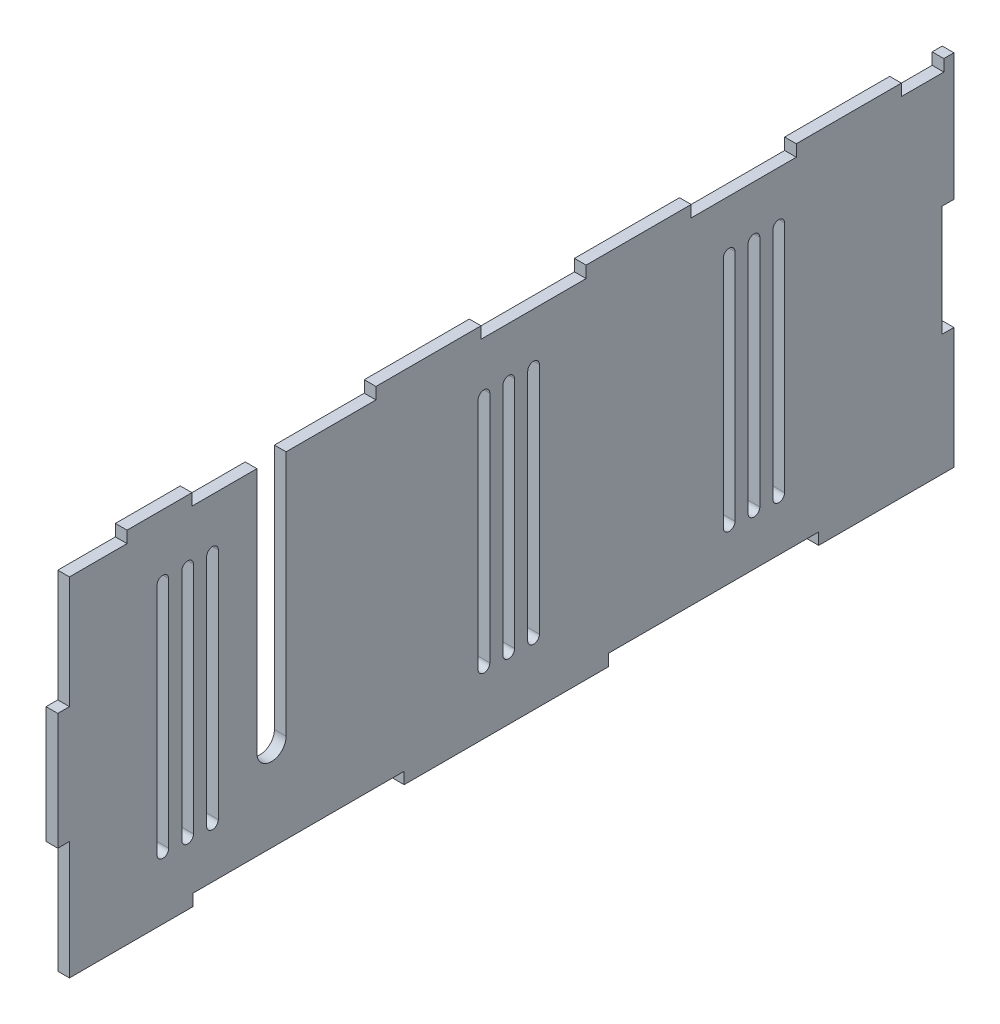
SolidWorks part; units mm, degrees
ref_plane "Front Plane" through (0, 0, 0) normal (0, 0, 1) x (1, 0, 0)
ref_plane "Top Plane" through (0, 0, 0) normal (0, 1, 0) x (1, 0, 0)
ref_plane "Right Plane" through (0, 0, 0) normal (1, 0, 0) x (0, 0, -1)
sketch "Sketch1" plane through (0, 0, 0) normal (1, 0, 0) x (0, 0, -1)
  line L1 (0, 0) -> (307, 0)
  line L2 (0, 0) -> (0, 115)
  line L3 (0, 115) -> (307, 115)
  line L4 (307, 0) -> (307, 115)
  dimension "D1" = 307
  dimension "D2" = 115
extrude "Boss-Extrude1" add sketch "Sketch1" along normal blind 4
sketch "Sketch2" plane through (0, 0, 0) normal (-1, 0, 0) x (0, 0, 1)
  line L0 (-73.2167, 30.5919) -> (-73.2167, 113) construction
  line L1 (-78.2167, 30.5919) -> (-78.2167, 118.2888)
  line L2 (-68.2167, 30.5919) -> (-68.2167, 118.2888)
  line L3 (-139, 113) -> (-121, 113) construction
  line L4 (-78.2167, 118.2888) -> (-68.2167, 118.2888)
  arc A0 (-78.2167, 30.5919) -> (-68.2167, 30.5919) centre (-73.2167, 30.5919) ccw
  point P2 (-73.2167, 71.796)
  point P7 (-73.2167, 113)
  dimension "D1" = 10
extrude "Cut-Extrude1" cut sketch "Sketch2" against normal blind 4
sketch "Sketch3" plane through (0, 0, 0) normal (-1, 0, 0) x (0, 0, 1)
  line L0 (0, 36.5) -> (0, -4)
  line L1 (0, 115) -> (-4, 115)
  line L2 (0, 115) -> (0, 76.5)
  line L3 (0, 76.5) -> (-4, 76.5)
  line L4 (-4, 115) -> (-4, 76.5)
  line L9 (0, 36.5) -> (-4, 36.5)
  line L10 (-4, 36.5) -> (-4, -4)
  line L11 (0, 115) -> (0, 0) construction
  line L12 (-68.2167, 115) -> (0, 115) construction
  line L13 (0, -4) -> (-4, -4)
  dimension "D1" = 4
  dimension "D2" = 38.5
  dimension "D3" = 40
extrude "Cut-Extrude2" cut sketch "Sketch3" against normal blind 4
sketch "Sketch4" plane through (0, 0, 0) normal (-1, 0, 0) x (0, 0, 1)
  line L1 (-307, 0) -> (-260.6667, 0)
  line L2 (-307, 0) -> (-307, -4)
  line L3 (-307, -4) -> (-260.6667, -4)
  line L4 (-260.6667, 0) -> (-260.6667, -4)
  line L11 (-4, 0) -> (-46.33, 0)
  line L12 (-4, 0) -> (-4, -4)
  line L13 (-4, -4) -> (-46.33, -4)
  line L14 (-46.33, 0) -> (-46.33, -4)
  dimension "D1" = 46.3333
  dimension "D2" = 4
  dimension "D3" = 42.33
  dimension "D4" = 4
extrude "Boss-Extrude3" add sketch "Sketch4" against normal blind 4 contours L2 L1 L4 L3 | L12 L11 L14 L13
sketch "Sketch5" plane through (0, 0, 0) normal (-1, 0, 0) x (0, 0, 1)
  line L0 (-307, 115) -> (-78.2167, 115) construction
  line L1 (-289, 115) -> (-253, 115)
  line L2 (-289, 115) -> (-289, 119)
  line L3 (-289, 119) -> (-253, 119)
  line L4 (-253, 115) -> (-253, 119)
  line L5 (-307, -4) -> (-307, 115) construction
  dimension "D1" = 4
  dimension "D2" = 36
  dimension "D3" = 18
extrude "Boss-Extrude4" add sketch "Sketch5" against normal blind 4
sketch "Sketch7" plane through (0, 0, 0) normal (-1, 0, 0) x (0, 0, 1)
  line L0 (-68.2167, 115) -> (-4, 115) construction
  line L1 (-45.9767, 115) -> (-23.7367, 115)
  line L2 (-45.9767, 115) -> (-45.9767, 119)
  line L3 (-45.9767, 119) -> (-23.7367, 119)
  line L4 (-23.7367, 115) -> (-23.7367, 119)
  line L5 (-68.2167, 30.5919) -> (-68.2167, 115) construction
  dimension "D1" = 22.24
  dimension "D2" = 22.24
  dimension "D3" = 4
extrude "Boss-Extrude6" add sketch "Sketch7" against normal blind 4
sketch "Sketch8" plane through (0, 0, 0) normal (-1, 0, 0) x (0, 0, 1)
  line L0 (-307, -4) -> (-307, 115) construction
  line L1 (-307, 75.5) -> (-303, 75.5)
  line L2 (-307, 75.5) -> (-307, 37.5)
  line L3 (-307, 37.5) -> (-303, 37.5)
  line L4 (-303, 75.5) -> (-303, 37.5)
  line L5 (-307, 115) -> (-289, 115) construction
  dimension "D1" = 38
  dimension "D2" = 39.5
extrude "Cut-Extrude3" cut sketch "Sketch8" against normal blind 4
pattern_linear "LPattern1" count 3 spacing 72 along (0, 0, 1) of "Boss-Extrude4"
sketch "Sketch9" plane through (0, 0, 0) normal (-1, 0, 0) x (0, 0, 1)
  line L0 (-46.33, 0) -> (-260.6667, 0) construction
  line L1 (-188.6667, 0) -> (-118.6667, 0)
  line L2 (-188.6667, 0) -> (-188.6667, -4)
  line L3 (-188.6667, -4) -> (-118.6667, -4)
  line L4 (-118.6667, 0) -> (-118.6667, -4)
  line L5 (-260.6667, 0) -> (-260.6667, -4) construction
  point P6 (-153.6667, 0)
  dimension "D1" = 70
  dimension "D2" = 107
  dimension "D3" = 4
extrude "Boss-Extrude7" add sketch "Sketch9" against normal blind 4
sketch "Sketch10" plane through (0, 0, 0) normal (-1, 0, 0) x (0, 0, 1)
  line L0 (-247, 97.5) -> (-247, 17.5) construction
  line L1 (-245, 97.5) -> (-245, 17.5)
  line L2 (-249, 97.5) -> (-249, 17.5)
  line L3 (-307, 75.5) -> (-307, 115) construction
  line L4 (-307, -4) -> (-260.6667, -4) construction
  line L6 (-240.5, 97.5) -> (-240.5, 17.5)
  line L7 (-236.5, 97.5) -> (-236.5, 17.5)
  line L8 (-238.5, 97.5) -> (-238.5, 17.5) construction
  line L9 (-232, 97.5) -> (-232, 17.5)
  line L10 (-228, 97.5) -> (-228, 17.5)
  line L11 (-230, 97.5) -> (-230, 17.5) construction
  arc A0 (-245, 97.5) -> (-249, 97.5) centre (-247, 97.5) ccw
  arc A1 (-249, 17.5) -> (-245, 17.5) centre (-247, 17.5) ccw
  arc A2 (-236.5, 97.5) -> (-240.5, 97.5) centre (-238.5, 97.5) ccw
  arc A3 (-240.5, 17.5) -> (-236.5, 17.5) centre (-238.5, 17.5) ccw
  arc A4 (-228, 97.5) -> (-232, 97.5) centre (-230, 97.5) ccw
  arc A5 (-232, 17.5) -> (-228, 17.5) centre (-230, 17.5) ccw
  point P2 (-247, 57.5)
  point P17 (-238.5, 57.5)
  point P24 (-230, 57.5)
  dimension "D1" = 4
  dimension "D2" = 58
  dimension "D3" = 80
  dimension "D4" = 61.5
extrude "Cut-Extrude4" cut sketch "Sketch10" against normal blind 4
pattern_linear "LPattern2" count 2 spacing 84 along (0, 0, 1) of "Cut-Extrude4"
pattern_linear "LPattern3" count 2 spacing 194 along (0, 0, 1) of "Cut-Extrude4"
sketch "Sketch11" plane through (0, 115, 0) normal (0, 1, 0) x (1, 0, 0)
  line L0 (0, 307) -> (0, 289) construction
  line L1 (4, 307) -> (0, 307)
  line L2 (4, 307) -> (4, 303.5424)
  line L3 (4, 303.5424) -> (0, 303.5424)
  line L4 (0, 307) -> (0, 303.5424)
extrude "Boss-Extrude8" add sketch "Sketch11" along normal blind 4
equation "\"Dikte\"= 4"
equation "\"D1@Sketch1\"=135+\"Dikte\" + 2*34 + 2*50"
equation "\"Tolerantie\"= 0.5"
equation "\"D2@Sketch3\"=39-\"Tolerantie\""
equation "\"D3@Sketch3\"=39+2*\"Tolerantie\""
equation "\"D2@Sketch8\"=39+\"Tolerantie\""
equation "\"D1@Sketch8\"=39-2*\"Tolerantie\""
